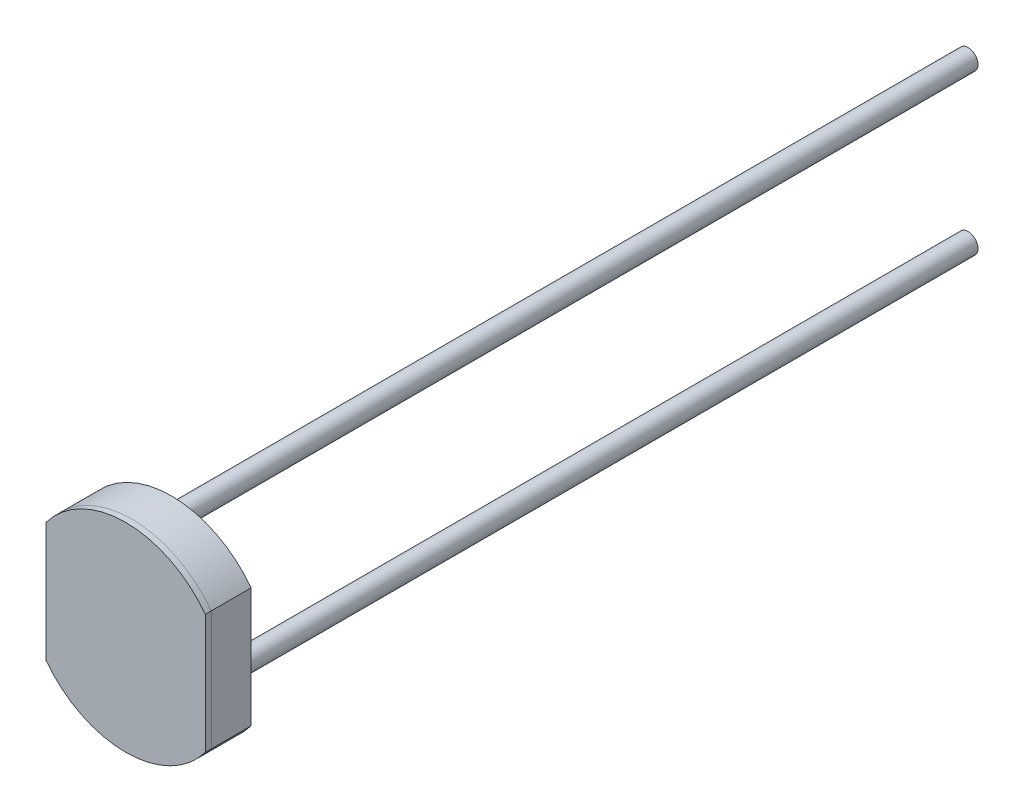
SolidWorks part; units mm, degrees
ref_plane "Front Plane" through (0, 0, 0) normal (0, 0, 1) x (1, 0, 0)
ref_plane "Top Plane" through (0, 0, 0) normal (0, 1, 0) x (1, 0, 0)
ref_plane "Right Plane" through (0, 0, 0) normal (1, 0, 0) x (0, 0, -1)
sketch "Sketch1" plane through (0, 0, 0) normal (0, 0, 1) x (1, 0, 0)
  line L6 (-2, 1.5) -> (-2, -1.5)
  line L8 (2, 1.5) -> (2, -1.5)
  arc A0 (2, 1.5) -> (-2, 1.5) centre (0, 0) ccw
  arc A1 (-2, -1.5) -> (2, -1.5) centre (0, 0) ccw
  dimension "D1" = 5
  dimension "D2" = 3
extrude "Boss-Extrude1" add sketch "Sketch1" along normal blind 1
sketch "Sketch3" plane through (0, 0, 1) normal (0, 0, 1) x (1, 0, 0)
  line L0 (-2.0874, 0) -> (2.0923, 0) construction
  line L1 (0, 2.6907) -> (0, -2.598) construction
  line L2 (-0.3, 1) -> (-0.3, 0)
  line L3 (0.3, 1) -> (0.3, 0)
  line L4 (0.3, 0) -> (0.3, -1)
  line L5 (0.9, -1) -> (0.9, 1)
  line L6 (1.5, 1) -> (1.5, 0)
  line L7 (2, -1.5) -> (2, 1.5) construction
  line L8 (-0.3, 0) -> (-0.3, -1)
  line L9 (-0.9, -1) -> (-0.9, 1)
  line L10 (-1.5, 1) -> (-1.5, 0)
  line L11 (-2, 1.5) -> (-2, -1.5) construction
  line L20 (1.6, 1) -> (1.6, 0)
  line L21 (0.8, -1) -> (0.8, 1)
  line L22 (0.4, 0) -> (0.4, -1)
  line L23 (0.4, 1) -> (0.4, 0)
  line L24 (-0.4, 1) -> (-0.4, 0)
  line L25 (-0.4, 0) -> (-0.4, -1)
  line L26 (-0.8, -1) -> (-0.8, 1)
  line L27 (-1.6, 1) -> (-1.6, 0)
  line L28 (1.4, 1) -> (1.4, 0)
  line L29 (1, -1) -> (1, 1)
  line L30 (0.2, 0) -> (0.2, -1)
  line L31 (0.2, 1) -> (0.2, 0)
  line L32 (-0.2, 1) -> (-0.2, 0)
  line L33 (-0.2, 0) -> (-0.2, -1)
  line L34 (-1, -1) -> (-1, 1)
  line L35 (-1.4, 1) -> (-1.4, 0)
  line L36 (2, -0.4) -> (2, -0.6)
  line L37 (-2, -0.4) -> (-2, -0.6)
  arc A0 (-0.3, 1) -> (0.3, 1) centre (0, 1) cw
  arc A1 (0.3, -1) -> (0.9, -1) centre (0.6, -1) ccw
  arc A2 (0.9, 1) -> (1.5, 1) centre (1.2, 1) cw
  arc A3 (1.5, 0) -> (2, -0.5) centre (2, 0) ccw
  arc A4 (-0.3, -1) -> (-0.9, -1) centre (-0.6, -1) cw
  arc A5 (-0.9, 1) -> (-1.5, 1) centre (-1.2, 1) ccw
  arc A6 (-1.5, 0) -> (-2, -0.5) centre (-2, 0) cw
  arc A14 (1.6, 0) -> (2, -0.4) centre (2, 0) ccw
  arc A15 (0.8, 1) -> (1.6, 1) centre (1.2, 1) cw
  arc A16 (0.4, -1) -> (0.8, -1) centre (0.6, -1) ccw
  arc A17 (-0.4, 1) -> (0.4, 1) centre (0, 1) cw
  arc A18 (-0.4, -1) -> (-0.8, -1) centre (-0.6, -1) cw
  arc A19 (-0.8, 1) -> (-1.6, 1) centre (-1.2, 1) ccw
  arc A20 (-1.6, 0) -> (-2, -0.4) centre (-2, 0) cw
  arc A21 (1.4, 0) -> (2, -0.6) centre (2, 0) ccw
  arc A22 (1, 1) -> (1.4, 1) centre (1.2, 1) cw
  arc A23 (0.2, -1) -> (1, -1) centre (0.6, -1) ccw
  arc A24 (-0.2, 1) -> (0.2, 1) centre (0, 1) cw
  arc A25 (-0.2, -1) -> (-1, -1) centre (-0.6, -1) cw
  arc A26 (-1, 1) -> (-1.4, 1) centre (-1.2, 1) ccw
  arc A27 (-1.4, 0) -> (-2, -0.6) centre (-2, 0) cw
  circle A28 centre (0, 2) radius 0.25
  circle A29 centre (0, -2) radius 0.25
  line M9 (2, -1.5) -> (2, 1.5)
  line M11 (-2, 1.5) -> (-2, -1.5)
  dimension "D2" = 0.3
  dimension "D6" = 0.5
  dimension "D7" = 2
  dimension "D1" = 1
  dimension "D4" = 0.1
  dimension "D5" = 0.1
extrude "Boss-Extrude2" add sketch "Sketch3" along normal blind 0.1 contours A27 L35 A26 L34 A25 L33 L32 A24 L31 L30 A23 L29 A22 L28 A21 A3 L6 A2 L5 A1 L4 L3 A0 L2 L8 A4 L9 A5 L10 A6 L37 M9 | L27 A20 A6 L10 A5 L9 A4 L8 L2 A0 L3 L4 A1 L5 A2 L6 A3 L36 A14 L20 A15 L21 A16 L22 L23 A17 L24 L25 A18 L26 A19 M11 | A29 | A28 region at (0, 1.2517, 1) region at (-0.3483, 0.5, 1) region at (0, 2, 1) region at (0, -2, 1)
fillet "Fillet1" radius 0.2 2 edges at (0.25, 2, 1.1) (0.25, -2, 1.1)
sketch "Sketch4" plane through (0, 0, 1) normal (0, 0, 1) x (1, 0, 0)
  line L0 (-2, -0.4) -> (-2, -0.6) construction
  line L1 (-2, -0.6) -> (-2, -1.5) construction
  line L2 (2, -1.5) -> (2, -0.6) construction
  line L3 (2, -0.6) -> (2, -0.4) construction
  line L4 (2, -0.4) -> (2, 1.5) construction
  line L5 (-2, 1.5) -> (-2, -0.4) construction
  line L6 (-2, -0.4) -> (-2, -0.6)
  line L7 (-2, -0.6) -> (-2, -1.5)
  line L8 (2, -1.5) -> (2, -0.6)
  line L9 (2, -0.6) -> (2, -0.4)
  line L10 (2, -0.4) -> (2, 1.5)
  line L11 (-2, 1.5) -> (-2, -0.4)
  arc A0 (-2, -1.5) -> (2, -1.5) centre (0, 0) ccw construction
  arc A1 (2, 1.5) -> (-2, 1.5) centre (0, 0) ccw construction
  arc A2 (-2, -1.5) -> (2, -1.5) centre (0, 0) ccw
  arc A3 (2, 1.5) -> (-2, 1.5) centre (0, 0) ccw
extrude "Boss-Extrude3" add sketch "Sketch4" along normal blind 0.15 separate body
sketch "Sketch5" plane through (0, 0, 0) normal (0, 0, -1) x (-1, 0, 0)
  line L0 (-2.4553, 0) -> (2.3685, 0) construction
  line L1 (0, 0) -> (0, 2.6131) construction
  circle A0 centre (0, 2) radius 0.25
  circle A1 centre (0, -2) radius 0.25
  dimension "D1" = 2
  dimension "D2" = 0.5
extrude "Boss-Extrude4" add sketch "Sketch5" along normal blind 20
